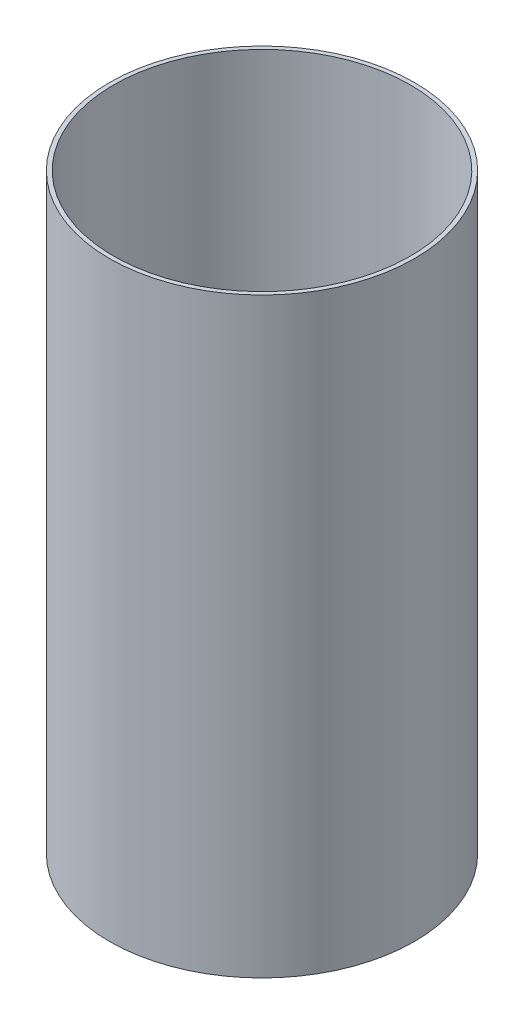
SolidWorks part; units mm, degrees
material "Hexcel AS4C (3000 Filaments)"
ref_plane "Front Plane" through (0, 0, 0) normal (0, 0, 1) x (1, 0, 0)
ref_plane "Top Plane" through (0, 0, 0) normal (0, 1, 0) x (1, 0, 0)
ref_plane "Right Plane" through (0, 0, 0) normal (1, 0, 0) x (0, 0, -1)
sketch "Sketch1" plane through (0, 0, 0) normal (0, 1, 0) x (1, 0, 0)
  circle A0 centre (0, 0) radius 76.454
  circle A1 centre (0, 0) radius 78.5876
  dimension "D1" = 152.908
  dimension "D2" = 157.1752
extrude "Boss-Extrude1" add sketch "Sketch1" along normal blind 304.8
